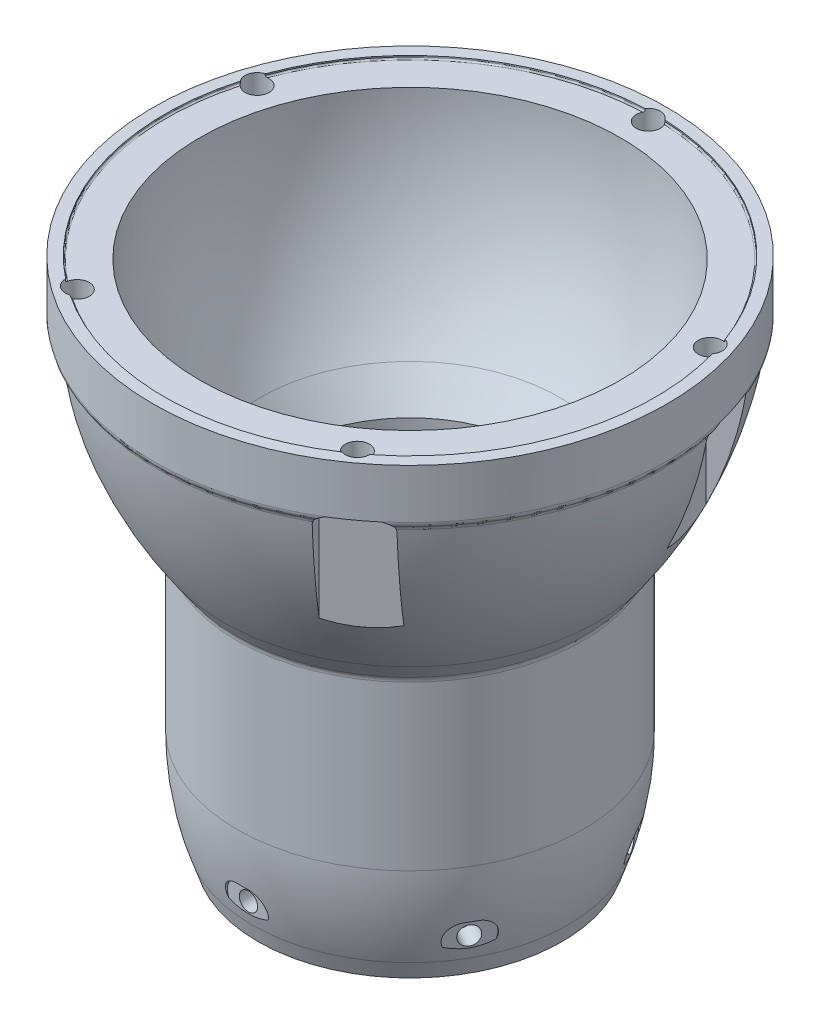
SolidWorks part; units mm, degrees
material "AISI 304"
ref_plane "Front Plane" through (0, 0, 0) normal (0, 0, 1) x (1, 0, 0)
ref_plane "Top Plane" through (0, 0, 0) normal (0, 1, 0) x (1, 0, 0)
ref_plane "Right Plane" through (0, 0, 0) normal (1, 0, 0) x (0, 0, -1)
sketch "Sketch4" plane through (0, 0, 0) normal (1, 0, 0) x (0, 0, -1)
  line L0 (0, 0) -> (0, -131.2074) construction
  line L1 (40.512, -52.769) -> (23.8732, -76.5317) construction
  line L2 (19.05, -81.8755) -> (19.05, -89.5492) construction
  line L3 (22.2956, -116.4815) -> (30.4091, -146.7615) construction
  line L4 (43.655, -238.5389) -> (49.5682, -351.369) construction
  line L5 (57.15, 0) -> (66.675, 0)
  line L6 (66.675, 0) -> (66.675, 0.762)
  line L7 (66.675, 0.762) -> (69.85, 0.762)
  line L11 (43.655, -238.5389) -> (48.3476, -238.293) construction
  line L16 (69.85, 0.762) -> (69.85, 0)
  line L17 (34.29, -61.655) -> (34.29, -86.7489)
  line L18 (34.29, -86.7489) -> (29.21, -86.7489)
  line L19 (29.21, -86.7489) -> (29.21, -107.7039)
  line L20 (29.21, -107.7039) -> (20.3822, -107.7039)
  line L21 (40.512, -52.769) -> (34.29, -61.655)
  line L22 (50.9152, -60.0535) -> (46.99, -65.6592)
  line L23 (46.99, -65.6592) -> (46.99, -123.4519)
  line L27 (69.85, 0) -> (69.85, -12.7)
  line L29 (37.3424, -124.2139) -> (38.1743, -140.0889)
  line L30 (38.1743, -140.0889) -> (41.3493, -140.0889)
  line L32 (36.412, -154.6514) -> (41.3493, -140.0889) construction
  line L33 (24.1344, -123.4519) -> (34.8024, -123.4519)
  line L34 (34.8024, -123.4519) -> (34.8024, -124.2139)
  line L35 (34.8024, -124.2139) -> (37.3424, -124.2139)
  line L36 (41.3493, -140.0889) -> (46.99, -123.4519)
  arc A0 (57.15, 0) -> (40.512, -52.769) centre (-34.85, 0) cw
  arc A1 (23.8732, -76.5317) -> (19.05, -91.8289) centre (45.72, -91.8289) ccw construction
  arc A2 (19.05, -91.8289) -> (22.2956, -116.4815) centre (114.3, -91.8289) ccw construction
  arc A4 (68.7524, -15.1206) -> (50.9152, -60.0535) centre (-34.85, 0) cw
  arc A5 (22.2956, -116.4815) -> (20.3822, -107.7039) centre (114.3, -91.8289) cw
  arc A6 (69.85, 0) -> (50.9152, -60.0535) centre (-34.85, 0) cw construction
  arc A7 (69.85, -12.7) -> (69.2912, -14.0479) centre (67.945, -12.7) cw
  arc A8 (69.2912, -14.0479) -> (68.7524, -15.1206) centre (70.6374, -15.3957) ccw
  parabola Q0 (22.2956, -116.4815) -> (43.655, -238.5389) focus (-29.3912, -334.2446) apex (5.2587, -370.9471) construction
  parabola Q1 (22.2956, -116.4815) -> (24.1344, -123.4519) focus (-29.3912, -334.2446) apex (5.2587, -370.9471)
  spline S0 degree 1 poles (26.8345, -115.2653) (48.3476, -238.293) knots 0 0 1 1 construction
  spline S1 degree 3 poles (26.8345, -115.2653) (27.2222, -116.7124) (27.9932, -119.6177) (29.4879, -125.3622) (31.281, -132.4698) (33.308, -140.8664) (34.849, -147.5602) (36.0157, -152.8165) (37.1872, -158.2271) (39.1632, -167.7678) (41.6472, -180.9811) (44.0897, -196.0997) (45.7108, -208.2706) (46.7587, -217.7507) (47.4201, -224.7336) (47.8672, -230.4437) (48.1627, -234.9534) (48.2891, -237.1769) (48.3476, -238.293) knots 0.493417 0.493417 0.493417 0.493417 0.493492 0.493567 0.493717 0.493867 0.494018 0.494082 0.494157 0.494318 0.494618 0.494918 0.495219 0.495369 0.495519 0.495669 0.495744 0.495819 0.495819 0.495819 0.495819 only from (36.412, -154.6514) to (48.3476, -238.293) construction
  dimension "D1" = 92
  dimension "D4" = 26.67
  dimension "D6" = 95.25
  dimension "D26" = 1.905
  dimension "D2" = 114.3
  dimension "D3" = 35
  dimension "D5" = 38.1
  dimension "D7" = 15
  dimension "D8" = 3
  dimension "D9" = 87.31
  dimension "D10" = 146.71
  dimension "D12" = 3.175
  dimension "D13" = 0.762
  dimension "D15" = 3.2456
  dimension "D19" = 10.16
  dimension "D20" = 5.08
  dimension "D21" = 15.875
  dimension "D22" = 12.7
  dimension "D11" = 68.58
  dimension "D24" = 58.42
  dimension "D23" = 12.7
  dimension "D28" = 3
  dimension "D30" = 3.175
  dimension "D32" = 2.54
  dimension "D27" = 16.51
  dimension "D31" = 0.762
  dimension "D29" = 15.875
  dimension "D16" = 13.208
  dimension "D14" = 4.699
  dimension "D18" = 12.7
revolve "Revolve1" add sketch "Sketch4" angle 360 about L0
fillet "Tool Radius" radius 0.4064 7 edges at (0, -107.7039, 29.21) (0, -86.7489, 34.29) (0, 0, 66.675) (0, -123.4519, 34.8024) (0, -124.2139, 37.3424) (0, -140.0889, 38.1743) (0, -86.7489, 29.21)
sketch "Sketch6" plane through (0, 0, 0) normal (1, 0, 0) x (0, 0, -1)
  line L0 (69.85, -12.7) -> (59.69, -12.7)
  line L1 (59.69, -12.7) -> (59.69, -44.992)
  line L2 (59.69, -44.992) -> (69.85, -44.992)
  line L3 (69.85, -44.992) -> (69.85, -12.7)
  line L4 (69.85, -12.7) -> (69.85, 0.762) construction
  line L5 (57.15, 0) -> (66.675, 0) construction
  line L6 (-69.85, -12.7) -> (69.85, -12.7) construction
  arc A0 (50.9152, -60.0535) -> (68.7524, -15.1206) centre (-34.85, 0) ccw construction
  arc A1 (50.9152, -60.0535) -> (68.7524, -15.1206) centre (-34.85, 0) ccw construction
  arc A2 (40.512, -52.769) -> (57.15, 0) centre (-34.85, 0) ccw construction
  arc A3 (40.512, -52.769) -> (57.15, 0) centre (-34.85, 0) ccw construction
  dimension "D1" = 10.16
  dimension "D3" = 12.7
extrude "Screw Flats" cut sketch "Sketch6" against normal mid plane 16.51
sketch "Sketch7" plane through (0, -12.7, 0) normal (0, -1, 0) x (1, 0, 0)
  line L0 (-8.255, -59.69) -> (8.255, -59.69) construction
  line L1 (-8.255, -59.69) -> (8.255, -59.69) construction
  circle A0 centre (0, -64.77) radius 3.2639
  arc A1 (-8.255, -69.3605) -> (8.255, -69.3605) centre (0, 0) ccw construction
  point P0 (0, -64.77)
  point P3 (0, -59.69)
  dimension "D2" = 6.5278
  dimension "D1" = 5.08
extrude "Screw Hole" cut sketch "Sketch7" against normal through all both and the other way through all
fillet "Flat Tool Radius" radius 3.302 2 edges at (-8.255, -12.7, -64.5252) (8.255, -12.7, -64.5252)
pattern_circular "CirPattern1" count 5 over 360 about axis through (0, 0, 0) along (0, 1, 0) of "Screw Flats", "Screw Hole", "Flat Tool Radius" reverse direction yes
sketch "Sketch11" plane through (0, 0, 0) normal (1, 0, 0) x (0, 0, -1)
  line L0 (46.99, -123.4519) -> (46.99, -140.0889) construction
ref_plane "Bottom Screw Planes" through (0, 0, -46.99) normal (0, 0, 1) x (1, 0, 0)
sketch "Sketch8" plane through (0, 0, -46.99) normal (0, 0, 1) x (1, 0, 0)
  line L0 (-36.9567, -124.2139) -> (36.9567, -124.2139) construction
  circle A0 centre (0, -129.2939) radius 2.4892
  dimension "D1" = 5.08
  dimension "D2" = 4.9784
extrude "Screw Holes" cut sketch "Sketch8" along normal up to next
sketch "Sketch10" plane through (0, 0, -46.99) normal (0, 0, 1) x (1, 0, 0)
  line L0 (1.27, -129.2939) -> (-1.27, -129.2939) construction
  line L1 (1.27, -133.7389) -> (-1.27, -133.7389)
  line L2 (1.27, -124.8489) -> (-1.27, -124.8489)
  arc A0 (1.27, -133.7389) -> (1.27, -124.8489) centre (1.27, -129.2939) ccw
  arc A1 (-1.27, -124.8489) -> (-1.27, -133.7389) centre (-1.27, -129.2939) ccw
  circle A2 centre (0, -129.2939) radius 2.4892 construction
  point P2 (0, -129.2939)
  dimension "D1" = 8.89
  dimension "D2" = 2.54
extrude "Flat" cut sketch "Sketch10" along normal blind 3.048
pattern_circular "CirPattern2" count 6 over 360 about axis through (0, -124.2139, 0) along (0, 1, 0) of "Screw Holes", "Flat" reverse direction yes
sketch "Sketch5" plane through (0, 0, 0) normal (1, 0, 0) x (0, 0, -1)
  line L0 (-34.29, -61.655) -> (34.29, -61.655) construction
  line L2 (-34.29, -61.655) -> (34.29, -61.655) construction
  line L3 (0, 34.2403) -> (0, 16.2865) construction
  line L4 (34.29, -68.005) -> (34.29, -69.91)
  line L5 (34.671, -69.91) -> (34.671, -68.005)
  line L6 (34.671, -68.005) -> (34.29, -68.005)
  line L7 (34.29, -69.91) -> (34.671, -69.91)
  dimension "D1" = 6.35
  dimension "D2" = 1.905
  dimension "D3" = 69.342
revolve "Spring Groove" cut sketch "Sketch5" angle 360 about L3
fillet "Convex Rounds" radius 76.2 1 edges at (0, -123.4519, 46.99)
fillet "Concave Rounds" radius 2.54 1 edges at (0, -65.6592, 46.99)
equation "\"D1@Sketch4\"=\"R2\""
equation "\"Dc\"= 114.30mm"
equation "\"D2@Sketch4\"=\"Dc\""
equation "\"Dt\"= 38.1mm"
equation "\"R1\"= 26.67mm"
equation "\"R2\"= 92mm"
equation "\"b\"= 35deg"
equation "\"Rn\"= 95.25mm"
equation "\"Tn\"= 15deg"
equation "\"Te\"= 3deg"
equation "\"De\"= 87.31mm"
equation "\"Le\"= 146.71mm"
equation "\"D4@Sketch4\"=\"R1\""
equation "\"D5@Sketch4\"=\"Dt\""
equation "\"D6@Sketch4\"=\"Rn\""
equation "\"D8@Sketch4\"=\"Te\""
equation "\"D9@Sketch4\"=\"De\""
equation "\"D10@Sketch4\"=\"Le\""
equation "\"WallThickness\"=0.5"
equation "\"D12@Sketch4\"=\"WallThickness\"/4"
equation "\"Rt\"=1.5"
